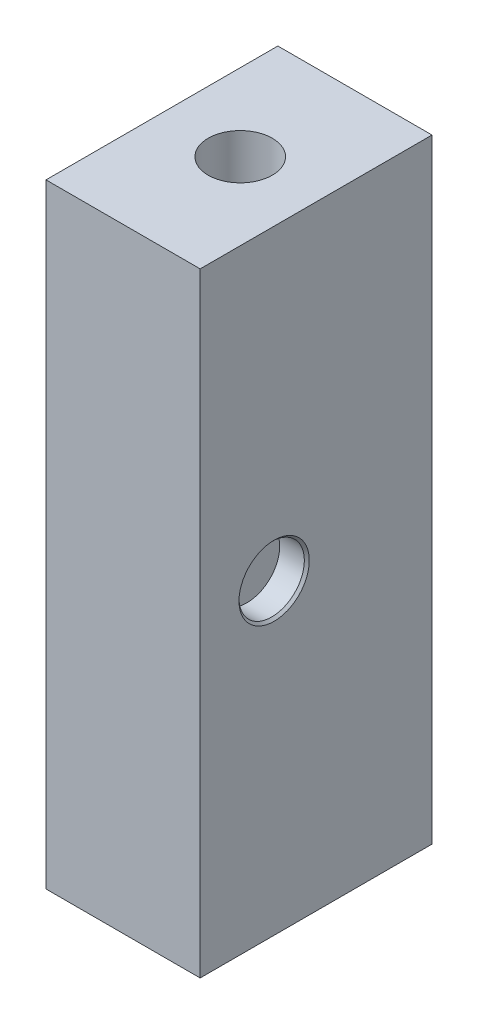
SolidWorks part; units mm, degrees
material "ABS"
ref_plane "Front Plane" through (0, 0, 0) normal (0, 0, 1) x (1, 0, 0)
ref_plane "Top Plane" through (0, 0, 0) normal (0, 1, 0) x (1, 0, 0)
ref_plane "Right Plane" through (0, 0, 0) normal (1, 0, 0) x (0, 0, -1)
sketch "Sketch1" plane through (0, 0, 0) normal (0, 1, 0) x (1, 0, 0)
  line L0 (-3.75, -9.5) -> (112.25, -9.5) construction
  line L1 (6.25, -9.5) -> (-6.25, -9.5)
  line L2 (6.25, -9.5) -> (6.25, 9.3)
  line L3 (6.25, 9.5) -> (-6.25, 9.5) construction
  line L4 (-6.25, -9.5) -> (-6.25, 9.3)
  line L5 (6.25, -9.5) -> (-6.25, 9.5) construction
  line L6 (6.1184, 9.3) -> (-6.25, -9.5) construction
  line L7 (114.75, 9.5) -> (-6.25, 9.5) construction
  line L8 (-6.25, 9.3) -> (6.25, 9.3)
  line L9 (-6.25, 9.3) -> (-6.25, 9.5) construction
  line L10 (6.25, 9.3) -> (6.25, 9.5) construction
  line L11 (6.25, 9.5) -> (6.1184, 9.3) construction
  circle A0 centre (0, 0) radius 2.6
  circle A1 centre (0, 0) radius 2.6 construction
  point P0 (0, 0)
  point P9 (0, 0.5653)
  dimension "D4" = 5.2
  dimension "D1" = 12.5
  dimension "D2" = 0.2
extrude "Boss-Extrude1" add sketch "Sketch1" along normal mid plane 49.8
sketch "Sketch2" plane through (6.25, 0, 0) normal (1, 0, 0) x (0, 0, -1)
  line L0 (-9.5, -24.9) -> (-9.5, 24.9) construction
  line L3 (9.5, -25) -> (9.5, 25) construction
  circle A0 centre (-3.5, 0) radius 2.65
  point P9 (9.5, -9.9914)
  dimension "D1" = 5.3
  dimension "D2" = 13
  dimension "D3" = 3.35
extrude "Cut-Extrude1" cut sketch "Sketch2" against normal blind 2.2
chamfer "Chamfer1" distance 0.2 angle 45 1 edges at (6.25, 0, 0.85)
